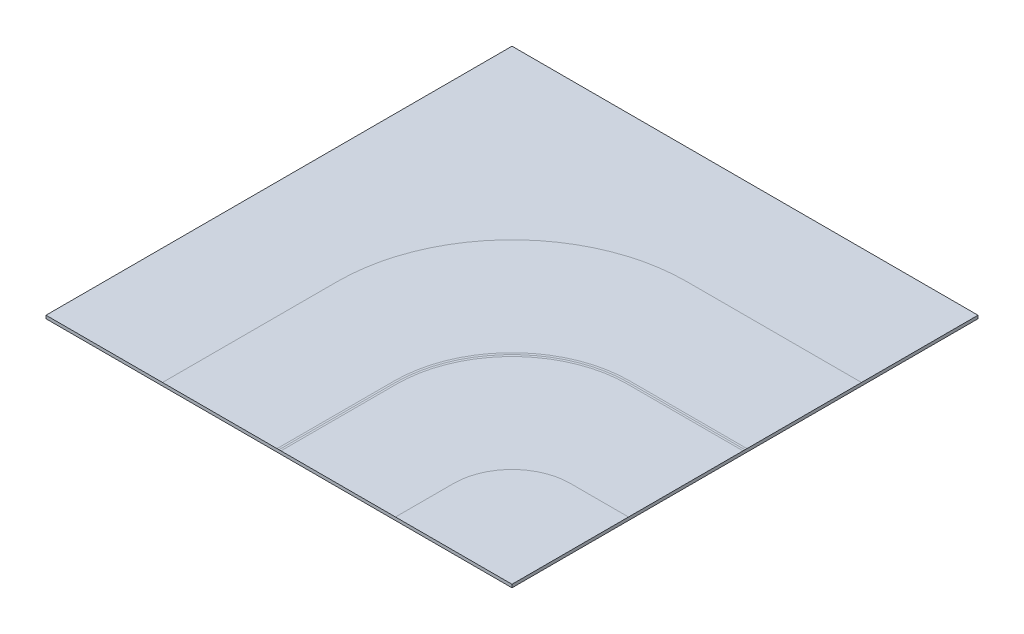
SolidWorks part; units mm, degrees
ref_plane "Front Plane" through (0, 0, 0) normal (0, 0, 1) x (1, 0, 0)
ref_plane "Top Plane" through (0, 0, 0) normal (0, 1, 0) x (1, 0, 0)
ref_plane "Right Plane" through (0, 0, 0) normal (1, 0, 0) x (0, 0, -1)
sketch "Sketch2" plane through (0, 0, 0) normal (0, 1, 0) x (1, 0, 0)
  line L0 (375, 0) -> (375, 562.5)
  line L1 (0, 0) -> (1500, 0)
  line L2 (0, 0) -> (0, 1500)
  line L3 (0, 1500) -> (1500, 1500)
  line L4 (1500, 0) -> (1500, 1500)
  line L5 (937.5, 1125) -> (1500, 1125)
  line L8 (1125, 0) -> (1125, 187.5)
  line L9 (1312.5, 375) -> (1500, 375)
  arc A3 (937.5, 1125) -> (375, 562.5) centre (937.5, 562.5) ccw
  arc A5 (1312.5, 375) -> (1125, 187.5) centre (1312.5, 187.5) ccw
  dimension "D1" = 1500
  dimension "D2" = 1500
  dimension "D3" = 375
extrude "Boss-Extrude2" add sketch "Sketch2" along normal blind 10 contours A3 L5 L4 L3 L2 L1 L0 | L4 L5 A3 L0 L1 | L1 L4 region at (508.394, 0, -991.606) region at (917.4551, 0, -582.5449) region at (1320.7554, 0, -179.2446)
sketch "Sketch3" plane through (0, 10, 0) normal (0, 1, 0) x (1, 0, 0)
  line L0 (750, 0) -> (750, 375)
  line L1 (0, 0) -> (1500, 0) construction
  line L2 (1125, 750) -> (1500, 750)
  line L3 (1121.875, 756.25) -> (1500, 756.25)
  line L9 (743.75, 0) -> (743.75, 378.125)
  line L10 (1500, 0) -> (1500, 1500) construction
  line L11 (756.25, 0) -> (756.25, 371.875)
  line L12 (1128.125, 743.75) -> (1500, 743.75)
  arc A0 (1125, 750) -> (750, 375) centre (1125, 375) ccw
  arc A1 (1121.875, 756.25) -> (743.75, 378.125) centre (1121.875, 378.125) ccw
  arc A3 (1128.125, 743.75) -> (756.25, 371.875) centre (1128.125, 371.875) ccw
  dimension "D1" = 6.25
  dimension "D2" = 6.25
  dimension "D3" = 6.25
split line "Split Line2"
split line "Split Line6"
sketch "Sketch2<16>" plane through (0, 0, 0) normal (0, 1, 0) x (1, 0, 0) same geometry as "Sketch2"
sketch "Sketch4" plane through (0, 10, 0) normal (0, 1, 0) x (1, 0, 0)
  line L2 (1500, 0) -> (1125, 0)
  line L4 (1500, 0) -> (1500, 375)
  line L5 (1500, 375) -> (1312.5, 375)
  line L6 (1125, 0) -> (1125, 187.5)
  arc A0 (1312.5, 375) -> (1125, 187.5) centre (1312.5, 187.5) ccw
split line "Split Line7"
equation "\"Scale\"= 8"
equation "\"Tile Size\"= \"Road Size\" * 2"
equation "\"Road Size\"= \"Real Lane Size\" * 2 / \"Scale\""
equation "\"Real Lane Size\"= 3m"
